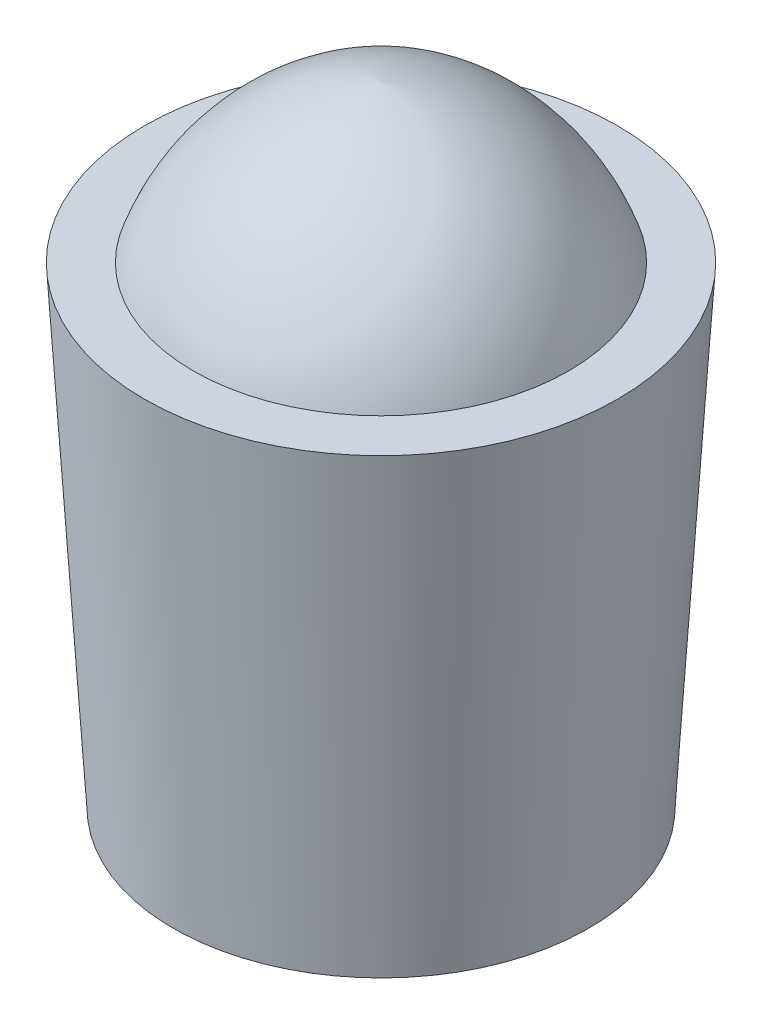
SolidWorks part; units mm, degrees
material "Nylon 101"
ref_plane "Front" through (0, 0, 0) normal (0, 0, 1) x (1, 0, 0)
ref_plane "Top" through (0, 0, 0) normal (0, 1, 0) x (1, 0, 0)
ref_plane "Right" through (0, 0, 0) normal (1, 0, 0) x (0, 0, -1)
ref_axis "Axis1" through (0, 0, 55) along (0, 0, -1)
sketch "Sketch1" plane through (0, 0, 0) normal (0, 0, 1) x (1, 0, 0)
  line L0 (0, 0) -> (0, 19.2117)
  line L1 (0, 0) -> (6.35, 0)
  line L2 (6.35, 0) -> (7.2319, 14.4436)
  line L3 (7.2319, 14.4436) -> (5.7391, 14.4436)
  arc A0 (0, 19.2117) -> (5.7391, 14.4436) centre (-1.0088, 12.1594) cw
  dimension "D2" = 7.124
  dimension "D1" = 6.35
  dimension "D3" = 5.7391
  dimension "D4" = 7.2319
  dimension "D5" = 1.0088
  dimension "D6" = 12.1594
revolve "Revolve1" add sketch "Sketch1" angle 360 about L0
